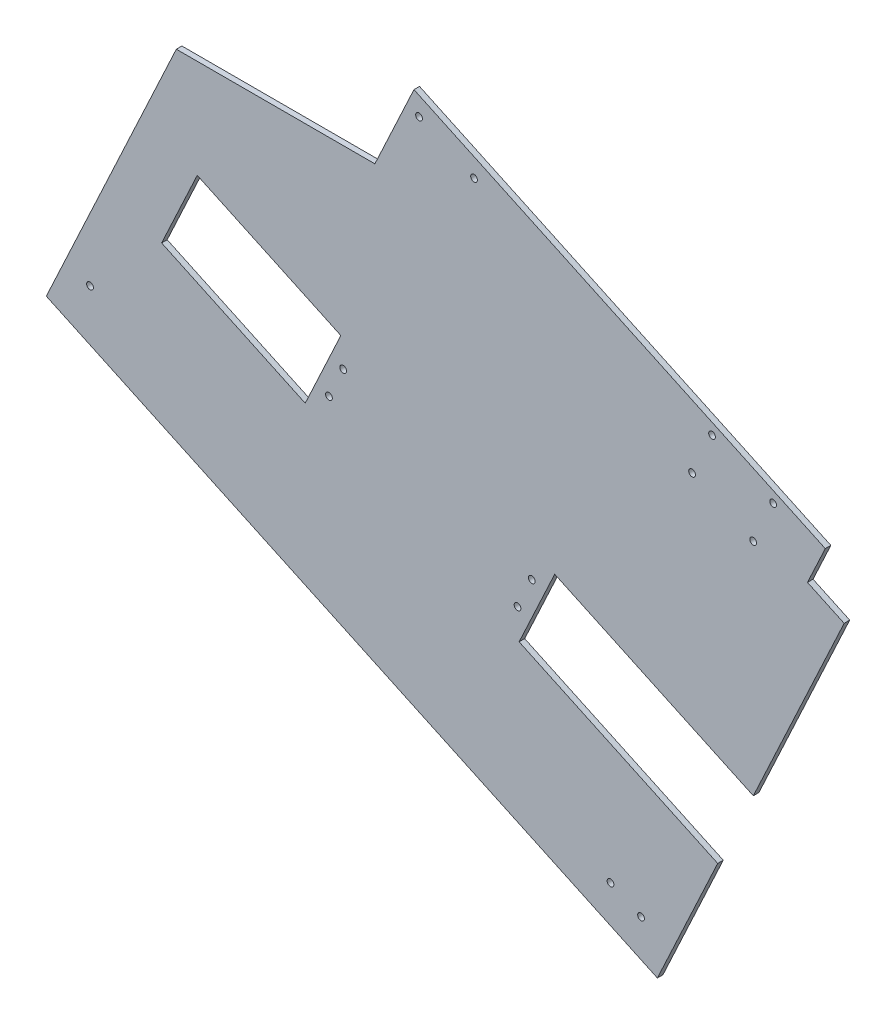
SolidWorks part; units mm, degrees
material "Balsa"
ref_plane "Front Plane" through (0, 0, 0) normal (0, 0, 1) x (1, 0, 0)
ref_plane "Top Plane" through (0, 0, 0) normal (0, 1, 0) x (1, 0, 0)
ref_plane "Right Plane" through (0, 0, 0) normal (1, 0, 0) x (0, 0, -1)
sketch "Sketch1" plane through (0, 0, 0) normal (0, 0, 1) x (1, 0, 0)
  line L0 (-255.2098, 12.6381) -> (-137.4275, 12.6381)
  line L1 (-137.4275, 12.6381) -> (-114.243, 62.3574)
  line L2 (-114.243, 62.3574) -> (129.7831, -51.4338)
  line L3 (129.7831, -51.4338) -> (119.2177, -74.0915)
  line L4 (119.2177, -74.0915) -> (140.969, -84.2344)
  line L5 (140.969, -84.2344) -> (30.1585, -321.8683)
  line L6 (30.1585, -321.8683) -> (-332.3646, -152.8209)
  line L7 (-332.3646, -152.8209) -> (-255.2098, 12.6381)
  line L9 (-332.3646, -152.8209) -> (-261.0998, 0.0069) construction
  line L10 (30.1585, -321.8683) -> (-332.3646, -152.8209) construction
  line L11 (140.969, -84.2344) -> (30.1585, -321.8683) construction
  line L12 (-189.2372, 97.3278) -> (129.7831, -51.4338) construction
  line L13 (119.2177, -74.0915) -> (140.969, -84.2344) construction
  line L14 (129.7831, -51.4338) -> (119.2177, -74.0915) construction
  circle A0 centre (87.0035, -69.0002) radius 2
  circle A1 centre (98.8369, -43.6236) radius 2
  circle A2 centre (62.5845, -26.7189) radius 2
  circle A3 centre (50.7512, -52.0955) radius 2
  circle A4 centre (2.3586, -286.8374) radius 2
  circle A5 centre (-306.4229, -134.5749) radius 2
  circle A6 centre (20.4847, -295.2897) radius 2
  circle A7 centre (2.3586, -286.8374) radius 2 construction
  circle A8 centre (20.4847, -295.2897) radius 2 construction
  point P0 (-137.4275, 12.6381)
  dimension "D1" = 4
  dimension "D2" = 4
  dimension "D3" = 4
  dimension "D4" = 4
  dimension "D7" = 4
  dimension "D5" = 27.5
  dimension "D6" = 15.8
extrude "Boss-Extrude1" add sketch "Sketch1" along normal up to surface (3.3 mm away)
sketch "Sketch2" plane through (0, 0, 0) normal (0, 0, -1) x (-1, 0, 0)
  line L0 (114.243, 62.3574) -> (137.4275, 12.6381) construction
  line L1 (-129.7831, -51.4338) -> (114.243, 62.3574) construction
  circle A0 centre (78.5916, 34.6991) radius 2
  circle A1 centre (111.2187, 49.9134) radius 2
  dimension "D1" = 4
  dimension "D2" = 4
  dimension "D3" = 8
  dimension "D4" = 36
  dimension "D5" = 10
  dimension "D6" = 10
extrude "Cut-Extrude1" cut sketch "Sketch2" against normal through all
sketch "Sketch5" plane through (0, 0, 3.3) normal (0, 0, 1) x (1, 0, 0)
  line L0 (65.9543, -245.104) -> (-51.8657, -190.1636)
  line L1 (140.969, -84.2344) -> (30.1585, -321.8683) construction
  line L2 (-51.8657, -190.1636) -> (-30.7348, -144.8482)
  line L3 (-30.7348, -144.8482) -> (87.0852, -199.7886)
  line L4 (87.0852, -199.7886) -> (65.9543, -245.104)
  line L5 (119.2177, -74.0915) -> (140.969, -84.2344) construction
  dimension "D1" = 130
  dimension "D2" = 127.5
  dimension "D3" = 50
extrude "Cut-Extrude2" cut sketch "Sketch5" against normal blind 10
sketch "Sketch6" plane through (0, 0, 3.3) normal (0, 0, 1) x (1, 0, 0)
  line L0 (-178.7488, -130.9971) -> (-157.6179, -85.6817)
  line L1 (-157.6179, -85.6817) -> (-242.8108, -45.9555)
  line L2 (-242.8108, -45.9555) -> (-263.9417, -91.2709)
  line L3 (-263.9417, -91.2709) -> (-178.7488, -130.9971)
  line L5 (87.0852, -199.7886) -> (-30.7348, -144.8482) construction
  line L6 (-51.8657, -190.1636) -> (65.9543, -245.104) construction
  line L7 (-332.3646, -152.8209) -> (-255.2098, 12.6381) construction
  line L8 (129.7831, -51.4338) -> (119.2177, -74.0915) construction
  dimension "D1" = 130
  dimension "D2" = 340
extrude "Cut-Extrude3" cut sketch "Sketch6" against normal blind 10
sketch "Sketch7" plane through (0, 0, 3.3) normal (0, 0, 1) x (1, 0, 0)
  circle A0 centre (-52.7985, -172.5711) radius 2
  circle A1 centre (-44.3462, -154.4449) radius 2
  circle A2 centre (-164.6725, -120.4034) radius 2
  circle A3 centre (-156.2202, -102.2772) radius 2
  circle A4 centre (-52.7985, -172.5711) radius 2 construction
  circle A5 centre (-44.3462, -154.4449) radius 2 construction
  circle A6 centre (-164.6725, -120.4034) radius 2 construction
  circle A7 centre (-156.2202, -102.2772) radius 2 construction
extrude "Cut-Extrude4" cut sketch "Sketch7" against normal blind 10
